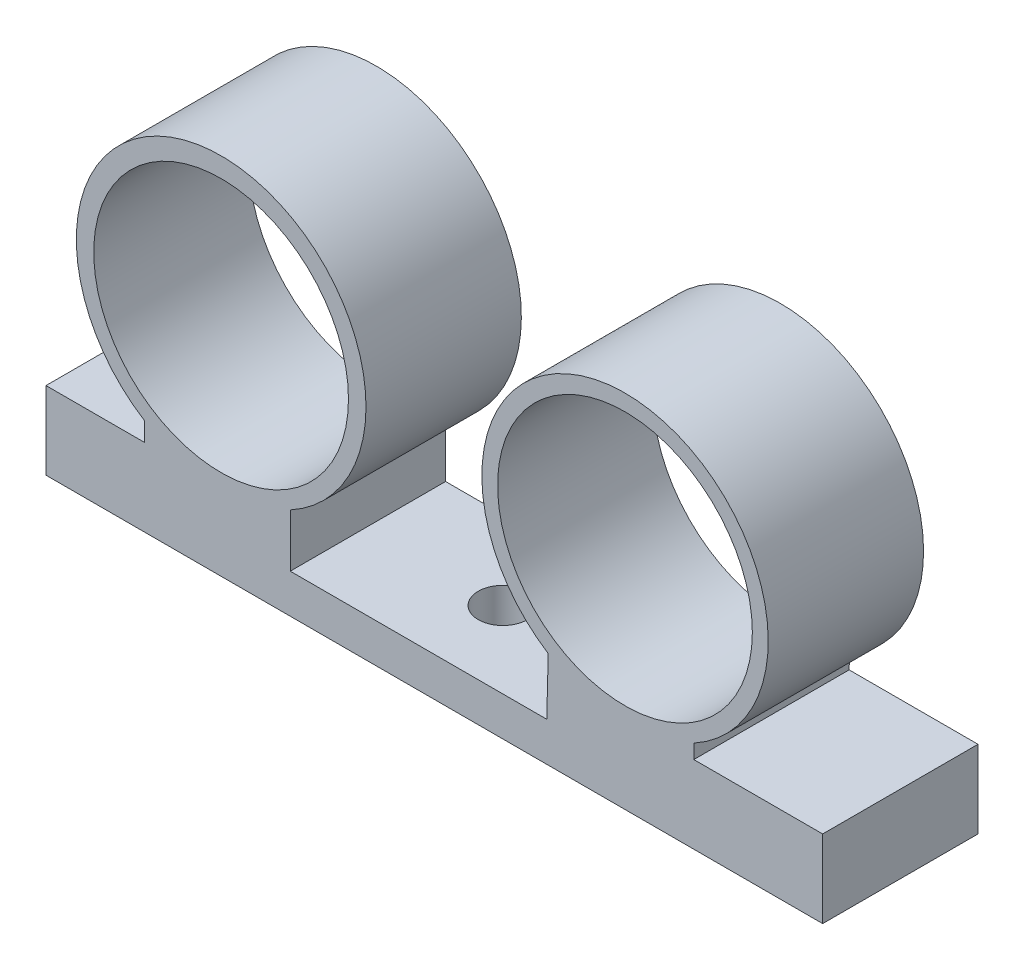
SolidWorks part; units mm, degrees
ref_plane "Alzado" through (0, 0, 0) normal (0, 0, 1) x (1, 0, 0)
ref_plane "Planta" through (0, 0, 0) normal (0, 1, 0) x (1, 0, 0)
ref_plane "Vista lateral" through (0, 0, 0) normal (1, 0, 0) x (0, 0, -1)
sketch "Sketch1" plane through (0, 0, 0) normal (0, 0, 1) x (1, 0, 0)
  line L0 (-4.1885, 12.6077) -> (-4.1885, 11.3881)
  line L1 (-10.5195, 6.3881) -> (39.4805, 6.3881)
  line L2 (-10.5195, 6.3881) -> (-10.5195, 11.3881)
  line L4 (39.4805, 6.3881) -> (39.4805, 11.3881)
  line L5 (-10.5195, 6.3881) -> (39.4805, 11.3881) construction
  line L6 (-10.5195, 11.3881) -> (39.4805, 6.3881) construction
  line L8 (5.2058, 8.9005) -> (5.2058, 12.317)
  line L9 (21.8133, 12.6118) -> (21.7176, 8.9005)
  line L11 (31.1849, 11.3881) -> (31.2089, 12.3192)
  line L12 (-10.5195, 11.3881) -> (-4.1885, 11.3881)
  line L13 (5.2058, 8.9005) -> (21.7176, 8.9005)
  line L14 (31.1849, 11.3881) -> (39.4805, 11.3881)
  circle A0 centre (26.7532, 20.3678) radius 8.2
  circle A1 centre (0.7532, 20.3678) radius 8.2
  arc A5 (-4.1885, 12.6077) -> (5.2058, 12.317) centre (0.7577, 20.5122) cw
  arc A6 (21.8133, 12.6118) -> (31.2089, 12.3192) centre (26.758, 20.391) cw
  point P4 (17.3377, 2.5)
  point P19 (31.4109, 9.0919)
  point P20 (-4.1885, 11.3881)
  point P21 (31.2089, 11.3881)
  dimension "D3" = 16.4
  dimension "D5" = 16.4
  dimension "D4" = 9.4
  dimension "D1" = 5
  dimension "D2" = 50
  dimension "D6" = 26
extrude "Boss-Extrude1" add sketch "Sketch1" along normal blind 10
sketch "Sketch2" plane through (0, 8.9005, 0) normal (0, 1, 0) x (1, 0, 0)
  circle A0 centre (13.9586, -5.0671) radius 1.585
  dimension "D1" = 3.17
extrude "Cut-Extrude1" cut sketch "Sketch2" against normal blind 10
